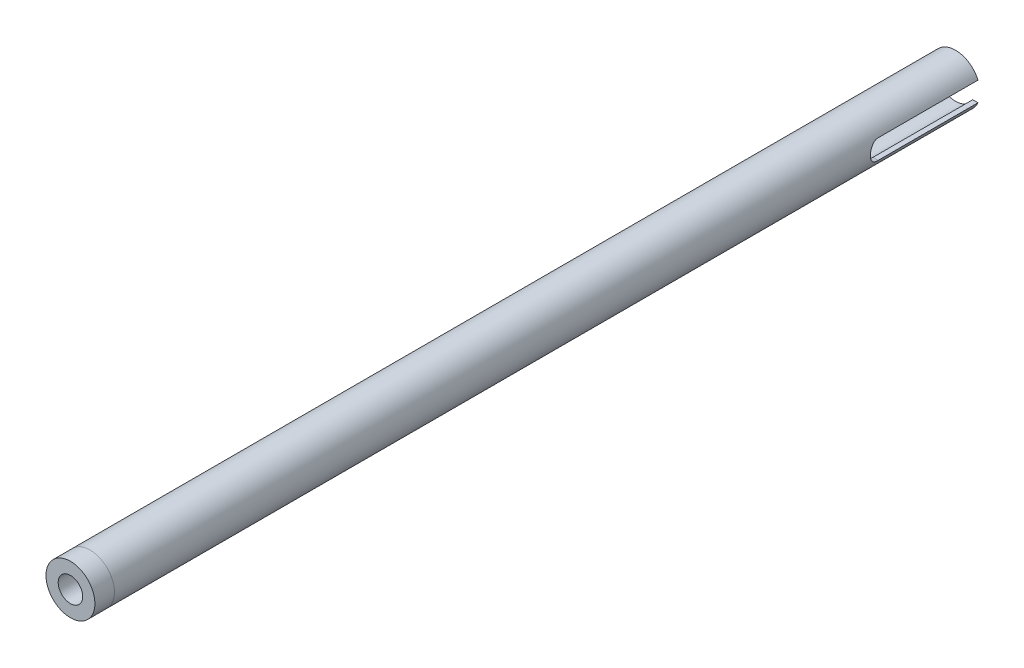
SolidWorks part; units mm, degrees
ref_plane "Front Plane" through (0, 0, 0) normal (0, 0, 1) x (1, 0, 0)
ref_plane "Top Plane" through (0, 0, 0) normal (0, 1, 0) x (1, 0, 0)
ref_plane "Right Plane" through (0, 0, 0) normal (1, 0, 0) x (0, 0, -1)
sketch "Axis" plane through (0, 0, 0) normal (0, 1, 0) x (1, 0, 0)
  line L0 (0, 0) -> (0, 287.1031) construction
  line L1 (0, 0) -> (0, -34.925) construction
  line L2 (0, 287.1031) -> (-7.9375, 287.1031) construction
  line L3 (0, 313.3089) -> (-28.3474, 219.7196) construction
  dimension "D1" = 34.925
  dimension "D2" = 7.9375
sketch "Sketch1" plane through (0, 0, 0) normal (0, 0, 1) x (1, 0, 0)
  line L0 (-7.9375, 0) -> (7.9375, 0) construction
  line L1 (-7.2748, 3.175) -> (7.2748, 3.175)
  line L2 (-7.2748, -3.175) -> (7.2748, -3.175)
  circle A0 centre (0, 0) radius 7.9375
  circle A1 centre (0, 0) radius 6.4135
  circle A2 centre (0, 0) radius 3.9688
  dimension "D1" = 15.875
  dimension "D3" = 7.9375
  dimension "D2" = 1.524
  dimension "D4" = 6.35
extrude "Threaded insert 1-1" add sketch "Sketch1" against normal blind 6.35 contours A2 L1 A1 | A1 L1 A0 | A2 L0 A1 L1 | A1 L0 A0 L1 | L0 A1 L2 A0 | L0 A2 L2 A1 | A2 L2 A1 | A1 L2 A0 | L0 A1 L2 A2 | L0 A0 L2 A1 | A0 L0 A1 L1 | A1 L0 A2 L1 region at (4.7887, 1.6543, 0) region at (4.7887, -1.6543, 0) region at (6.9234, 1.6163, 0) region at (6.9234, -1.6163, 0) region at (-4.7887, -1.6543, 0) region at (-4.7887, 1.6543, 0) region at (0, 4.6159, 0) region at (0, -4.6159, 0) region at (0, 6.5666, 0) region at (6.4237, -3.3281, 0) region at (-6.9234, -1.6163, 0) region at (-6.9234, 1.6163, 0)
extrude "Threaded insert 1-2" add sketch "Sketch1<3>" against normal blind 9.525 from surface contours A2 L1 A1 | A2 L0 A1 L1 | L0 A2 L2 A1 | A2 L2 A1 | L0 A1 L2 A2 | A1 L0 A2 L1 region at (4.7887, 1.6543, 0) region at (4.7887, -1.6543, 0) region at (-4.7887, -1.6543, 0) region at (-4.7887, 1.6543, 0) region at (0, 4.6159, 0) region at (0, -4.6159, 0) starting at face at (7.9375, 0, -6.35)
sketch "Sketch1<3>" plane through (0, 0, 0) normal (0, 0, 1) x (1, 0, 0) same geometry as "Sketch1"
extrude "A-arm tube" add sketch "Sketch1<4>" against normal up to vertex (287.1031 mm away) from surface separate body contours A1 L1 A0 | A1 L0 A0 L1 | L0 A1 L2 A0 | A1 L2 A0 | L0 A0 L2 A1 | A0 L0 A1 L1 region at (6.9234, 1.6163, 0) region at (6.9234, -1.6163, 0) region at (0, 6.5666, 0) region at (6.4237, -3.3281, 0) region at (-6.9234, -1.6163, 0) region at (-6.9234, 1.6163, 0) up to point (0, 0, -287.1031) starting at face at (6.4135, 0, -6.35)
sketch "Sketch1<4>" plane through (0, 0, 0) normal (0, 0, 1) x (1, 0, 0) same geometry as "Sketch1"
extrude "Apex slot" cut sketch "Sketch1<5>" along normal blind 35.56 from surface contours A0 L0 A1 L1 | L0 A0 L2 A1 | A1 L0 A0 L1 | L0 A1 L2 A0 region at (6.9234, 1.6163, 0) region at (6.9234, -1.6163, 0) region at (-6.9234, -1.6163, 0) region at (-6.9234, 1.6163, 0) starting at face at (6.4135, 0, -287.1031)
sketch "Sketch1<5>" plane through (0, 0, 0) normal (0, 0, 1) x (1, 0, 0) same geometry as "Sketch1"
fillet "Fillet1" radius 3.175 4 edges at (-6.4237, 3.175, -251.5431) (-6.4237, -3.175, -251.5431) (6.4237, -3.175, -251.5431) (6.4237, 3.175, -251.5431)
equation "\"tube diameter\"= 5 / 8"
equation "\"tube thickness\"= .06"
equation "\"apex thickness\"= .25"
equation "\"tube slot\"= 1.4"
equation "\"D1@Sketch1\"=\"tube diameter\""
equation "\"D2@Sketch1\"=\"tube thickness\""
equation "\"threaded insert hole\"= .3125"
equation "\"D3@Sketch1\"=\"threaded insert hole\""
equation "\"D4@Sketch1\"=\"apex thickness\""
equation "\"D1@Apex slot\" = \"tube slot\""
equation "\"D1@Fillet1\"=\"apex thickness\"/2"
equation "\"D2@Axis\"=\"tube diameter\"/2"
